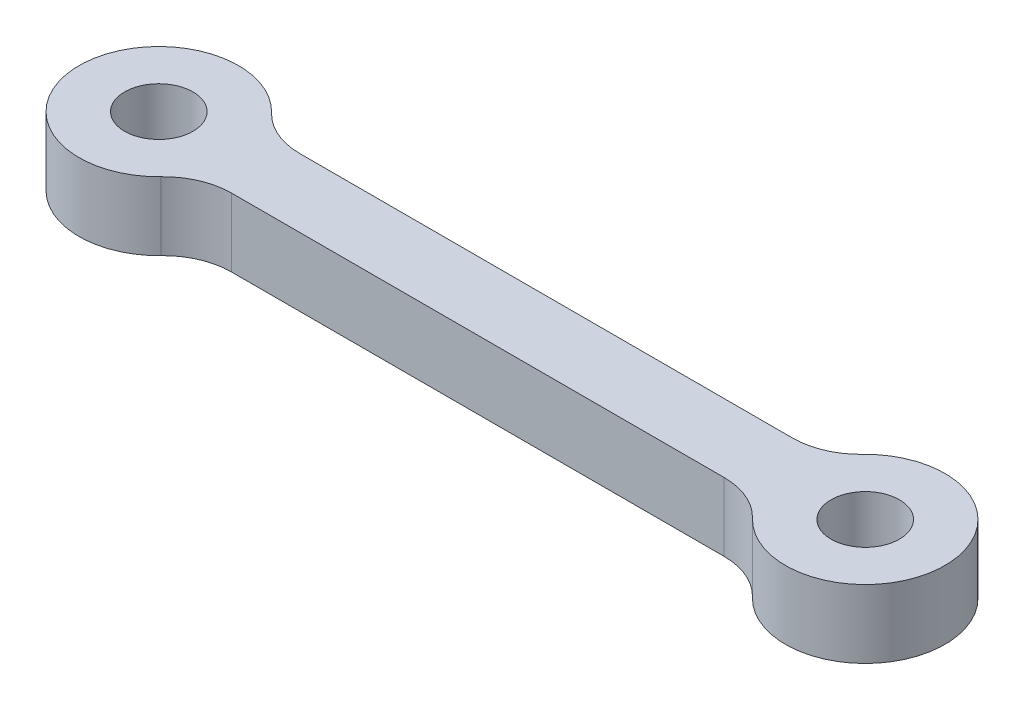
SolidWorks part; units mm, degrees
ref_plane "Front Plane" through (0, 0, 0) normal (0, 0, 1) x (1, 0, 0)
ref_plane "Top Plane" through (0, 0, 0) normal (0, 1, 0) x (1, 0, 0)
ref_plane "Right Plane" through (0, 0, 0) normal (1, 0, 0) x (0, 0, -1)
sketch "Sketch1" plane through (0, 0, 0) normal (0, 1, 0) x (1, 0, 0)
  line L0 (0, 0) -> (31, 0) construction
  line L1 (3.1623, 1.5) -> (27.8377, 1.5)
  line L2 (3.1623, -1.5) -> (27.8377, -1.5)
  circle A0 centre (0, 0) radius 3.5
  circle A1 centre (31, 0) radius 3.5
  circle A2 centre (0, 0) radius 1.5
  circle A3 centre (31, 0) radius 1.5
  dimension "D1" = 7
  dimension "D3" = 7
  dimension "D5" = 3
  dimension "D6" = 3
  dimension "D2" = 31
  dimension "D4" = 1.5
extrude "Boss-Extrude1" add sketch "Sketch1" along normal blind 3 contours A2 A0 | L0 A0 L2 A1 | A0 L0 A1 L1 | A1 A3 region at (3.3179, 0, 0.747) region at (15.5, 0, -0.7534) region at (15.5, 0, 0.7534) region at (27.6821, 0, -0.747)
fillet "Fillet1" radius 3 4 edges at (3.1623, 1.5, 1.5) (27.8377, 1.5, 1.5) (27.8377, 1.5, -1.5) (3.1623, 1.5, -1.5)
